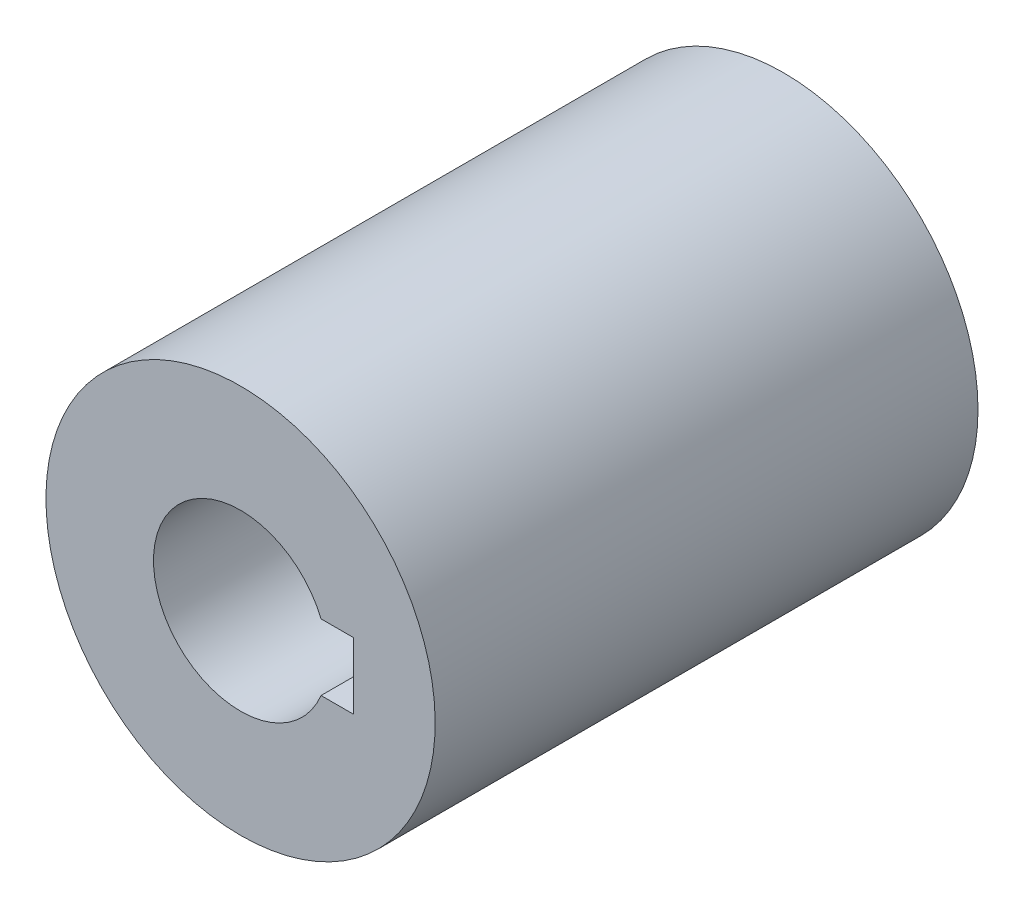
SolidWorks part; units mm, degrees
ref_plane "Front Plane" through (0, 0, 0) normal (0, 0, 1) x (1, 0, 0)
ref_plane "Top Plane" through (0, 0, 0) normal (0, 1, 0) x (1, 0, 0)
ref_plane "Right Plane" through (0, 0, 0) normal (1, 0, 0) x (0, 0, -1)
sketch "Sketch2" plane through (0, 0, 0) normal (0, 0, 1) x (1, 0, 0)
  line L1 (0, -7.5056) -> (6.5, -3.7528)
  line L2 (6.5, -3.7528) -> (6.5, 3.7528)
  line L3 (6.5, 3.7528) -> (0, 7.5056)
  line L4 (0, 7.5056) -> (-6.5, 3.7528)
  line L5 (-6.5, 3.7528) -> (-6.5, -3.7528)
  line L6 (-6.5, -3.7528) -> (0, -7.5056)
  circle A0 centre (0, 0) radius 6.5 construction
  circle A1 centre (0, 0) radius 4.25
  circle A2 centre (0, 0) radius 9.5
  dimension "D2" = 8.5
  dimension "D3" = 19
  dimension "D1" = 13
extrude "Boss-Extrude1" add sketch "Sketch2" against normal up to surface (21 mm away) contours A2 L6 L5 L4 L3 L2 L1 region at (-9.2313, 0, 0)
sketch "Sketch3" plane through (0, 0, 0) normal (0, 0, 1) x (1, 0, 0)
  line L0 (-6.5, -3.7528) -> (0, -7.5056) construction
  line L1 (-6.5, 3.7528) -> (-6.5, -3.7528) construction
  line L2 (0, 7.5056) -> (-6.5, 3.7528) construction
  line L3 (6.5, 3.7528) -> (0, 7.5056) construction
  line L4 (6.5, -3.7528) -> (6.5, 3.7528) construction
  line L5 (0, -7.5056) -> (6.5, -3.7528) construction
  line L6 (-6.5, -3.7528) -> (0, -7.5056)
  line L7 (-6.5, 3.7528) -> (-6.5, -3.7528)
  line L8 (0, 7.5056) -> (-6.5, 3.7528)
  line L9 (6.5, 3.7528) -> (0, 7.5056)
  line L10 (6.5, -3.7528) -> (6.5, 3.7528)
  line L11 (0, -7.5056) -> (6.5, -3.7528)
  circle A0 centre (0, 0) radius 4.25
  dimension "D1" = 8.5
extrude "Boss-Extrude2" add sketch "Sketch3" against normal blind 5 contours L6 L11 L10 L9 L8 L7 | A0
sketch "Sketch4" plane through (0, 0, 0) normal (0, 0, 1) x (1, 0, 0)
  line L0 (3.6194, 1.37) -> (5.27, 1.37)
  line L1 (5.27, 1.37) -> (5.27, -1.37)
  line L2 (5.27, -1.37) -> (3.6194, -1.37)
  line L3 (5.52, -1.62) -> (3.7881, -1.62)
  line L4 (3.7881, 1.62) -> (5.52, 1.62)
  line L5 (5.52, 1.62) -> (5.52, -1.62)
  arc A0 (3.6194, 1.37) -> (3.6194, -1.37) centre (0, 0) ccw construction
  arc A1 (3.6194, 1.37) -> (3.6194, -1.37) centre (0, 0) ccw
  arc A2 (3.8532, 1.4585) -> (3.8532, -1.4585) centre (0, 0) ccw
  arc A3 (3.7881, 1.62) -> (3.7881, -1.62) centre (0, 0) ccw
  circle A4 centre (0, 0) radius 9.5
  circle M2 centre (0, 0) radius 9.5
  circle M3 centre (0, 0) radius 4.25
  dimension "D1" = 0.25
  dimension "D2" = 0.25
extrude "Boss-Extrude3" add sketch "Sketch4" along normal up to surface (10 mm away) contours L4 L5 L3 M2 M3 region at (-9.2313, 0, 0)
sketch "Sketch5" plane through (0, 0, -21) normal (0, 0, -1) x (-1, 0, 0)
  circle A1 centre (0, 0) radius 9.5
  circle A2 centre (0, 0) radius 9.5
  dimension "D1" = 0
extrude "Cut-Extrude1" cut sketch "Sketch5" against normal blind 7.5
sketch "Sketch6" plane through (0, 0, -13.5) normal (0, 0, -1) x (-1, 0, 0)
  line L0 (6.5, 3.7528) -> (6.5, -3.7528) construction
  line L1 (6.5, -3.7528) -> (0, -7.5056) construction
  line L2 (0, -7.5056) -> (-6.5, -3.7528) construction
  line L3 (-6.5, -3.7528) -> (-6.5, 3.7528) construction
  line L4 (-6.5, 3.7528) -> (0, 7.5056) construction
  line L5 (0, 7.5056) -> (6.5, 3.7528) construction
  line L6 (6.5, 3.7528) -> (6.5, -3.7528)
  line L7 (6.5, -3.7528) -> (0, -7.5056)
  line L8 (0, -7.5056) -> (-6.5, -3.7528)
  line L9 (-6.5, -3.7528) -> (-6.5, 3.7528)
  line L10 (-6.5, 3.7528) -> (0, 7.5056)
  line L11 (0, 7.5056) -> (6.5, 3.7528)
  circle A1 centre (0, 0) radius 9.5
  circle A2 centre (0, 0) radius 9.5
  dimension "D1" = 0
extrude "Boss-Extrude4" add sketch "Sketch6" along normal blind 3
